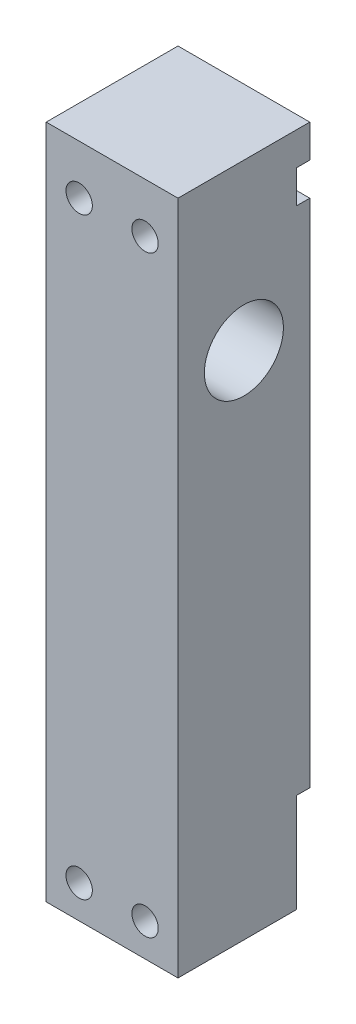
SolidWorks part; units mm, degrees
ref_plane "Front Plane" through (0, 0, 0) normal (0, 0, 1) x (1, 0, 0)
ref_plane "Top Plane" through (0, 0, 0) normal (0, 1, 0) x (1, 0, 0)
ref_plane "Right Plane" through (0, 0, 0) normal (1, 0, 0) x (0, 0, -1)
sketch "Sketch1" plane through (0, 0, 0) normal (1, 0, 0) x (0, 0, -1)
  line L0 (0, 55) -> (0, -55) construction
  line L1 (0, 120) -> (20, 120)
  line L2 (0, 120) -> (0, 0)
  line L3 (0, 0) -> (20, 0)
  line L4 (20, 120) -> (20, 0)
  line L5 (55, 0) -> (-55, 0) construction
  circle A2 centre (10, 82.5) radius 6
  dimension "D3" = 12
  dimension "D4" = 37.5
  dimension "D5" = 10
  dimension "D1" = 20
  dimension "D2" = 120
extrude "Boss-Extrude2" add sketch "Sketch1" against normal blind 20
ref_plane "Plane1" through (0, 0, 0) normal (1, 0, 0) x (0, 0, -1)
ref_plane "Plane2" through (0, 0, 0) normal (0, 0, 1) x (1, 0, 0)
sketch "Sketch11" plane through (0, 0, 0) normal (0, 0, 1) x (1, 0, 0)
  line L0 (-10, 120) -> (-10, 0)
  line L1 (-20, 120) -> (0, 120) construction
  line L2 (55, 0) -> (-55, 0) construction
  line L3 (-20, 120) -> (-20, 0) construction
  line L4 (-20, 0) -> (0, 0) construction
  circle A0 centre (-15, 10) radius 1
  circle A1 centre (-5, 10) radius 1
  circle A2 centre (-15, 100) radius 1
  circle A3 centre (-5, 100) radius 1
  dimension "D1" = 2
  dimension "D4" = 2
  dimension "D2" = 5
  dimension "D3" = 10
  dimension "D5" = 100
extrude "Cut-Extrude2" cut sketch "Sketch11" against normal through all contours A0 | A1 | A0 region at (-15, 10, 0) region at (-5, 10, 0)
ref_plane "Plane3" through (0, 0, 0) normal (0, 0, 1) x (1, 0, 0)
sketch "Sketch12" plane through (0, 0, 0) normal (0, 0, 1) x (1, 0, 0)
  line L0 (55, 0) -> (-55, 0) construction
  circle A0 centre (-15, 10) radius 2
  circle A1 centre (-5, 10) radius 2
  circle A2 centre (-15, 100) radius 2
  circle A3 centre (-5, 100) radius 2
  dimension "D1" = 4
  dimension "D2" = 4
  dimension "D3" = 4
  dimension "D4" = 4
  dimension "D5" = 100
  dimension "D6" = 100
extrude "Cut-Extrude3" cut sketch "Sketch12" against normal blind 5
extrude "Cut-Extrude4" cut sketch "Sketch11<3>" against normal through all contours A2 | A3
sketch "Sketch11<3>" plane through (0, 0, 0) normal (0, 0, 1) x (1, 0, 0) same geometry as "Sketch11"
ref_plane "Plane4" through (0, 0, -20) normal (0, 0, -1) x (-1, 0, 0)
sketch "Sketch14" plane through (0, 0, -20) normal (0, 0, -1) x (-1, 0, 0)
  line L0 (55, 0) -> (-55, 0) construction
  line L1 (0, 102.5) -> (20, 102.5)
  line L2 (0, 102.5) -> (0, 97.5)
  line L3 (0, 97.5) -> (20, 97.5)
  line L4 (20, 102.5) -> (20, 97.5)
  line L5 (0, 102.5) -> (20, 97.5) construction
  line L6 (0, 97.5) -> (20, 102.5) construction
  line L7 (0, 20) -> (20, 20)
  line L8 (0, 20) -> (0, 0)
  line L9 (0, 0) -> (20, 0)
  line L10 (20, 20) -> (20, 0)
  line L11 (0, 20) -> (20, 0) construction
  line L12 (0, 0) -> (20, 20) construction
  line L13 (20, 0) -> (20, 120) construction
  point P0 (10, 100)
  point P5 (10, 10)
  dimension "D1" = 100
  dimension "D2" = 10
  dimension "D3" = 20
  dimension "D4" = 5
  dimension "D5" = 20
  dimension "D6" = 20
  dimension "D7" = 10
  dimension "D8" = 10
extrude "Cut-Extrude6" cut sketch "Sketch14" against normal blind 2
ref_plane "Plane5" through (0, 0, 0) normal (1, 0, 0) x (0, 0, -1)
sketch "Sketch15" plane through (0, 0, 0) normal (1, 0, 0) x (0, 0, -1)
  line L0 (18, 20) -> (18, 0) construction
  line L1 (0, 0) -> (18, 0)
  line L2 (0, 0) -> (0, 5)
  line L3 (0, 5) -> (18, 5)
  line L4 (18, 0) -> (18, 5)
  dimension "D1" = 5
extrude "Cut-Extrude7" cut sketch "Sketch15" against normal through all
ref_plane "Plane6" through (0, 0, -20) normal (0, 0, -1) x (-1, 0, 0)
sketch "Sketch16" plane through (0, 0, -20) normal (0, 0, -1) x (-1, 0, 0)
  line L0 (0, 11) -> (0, -11) construction
  line L1 (0, 107.5) -> (20, 107.5)
  line L2 (0, 107.5) -> (0, 120)
  line L3 (0, 120) -> (20, 120)
  line L4 (20, 107.5) -> (20, 120)
  line L5 (20, 102.5) -> (20, 120) construction
  line L6 (20, 120) -> (0, 120) construction
  line L7 (20, 102.5) -> (0, 102.5) construction
  dimension "D1" = 5
extrude "Cut-Extrude8" cut sketch "Sketch16" against normal through all
